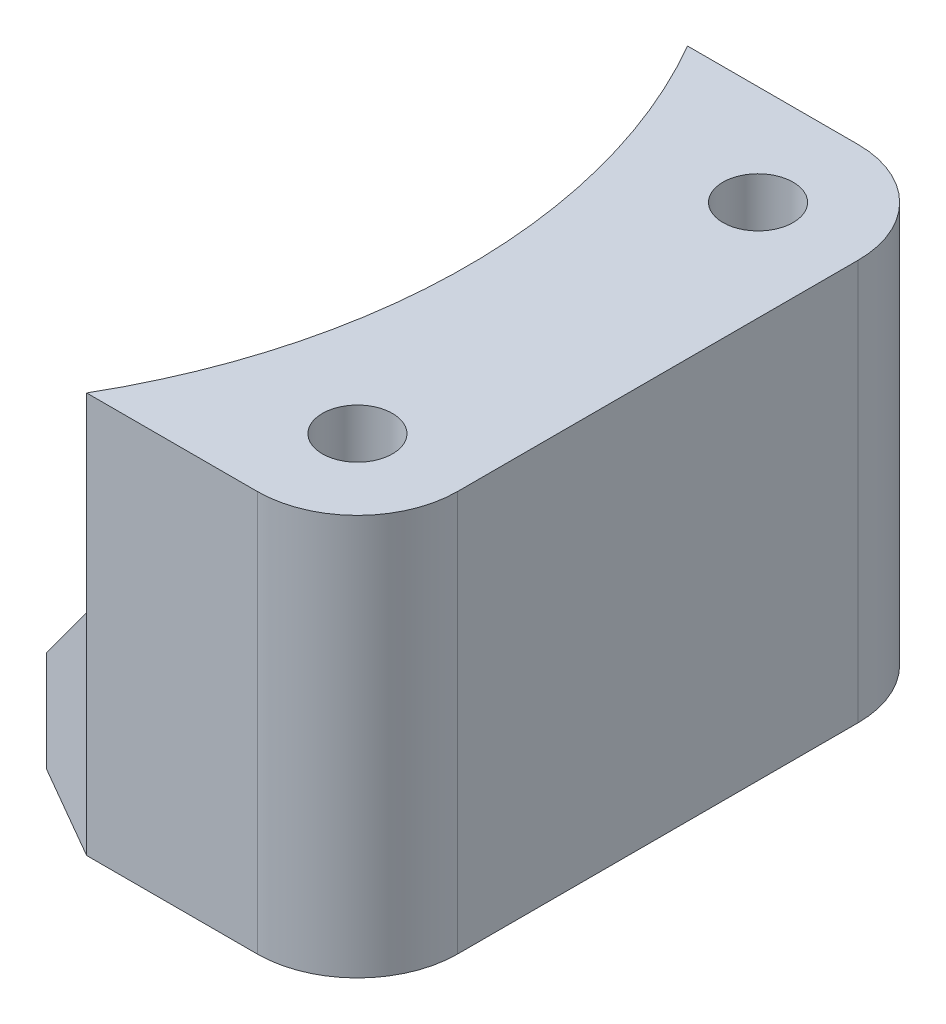
SolidWorks part; units mm, degrees
ref_plane "Front Plane" through (0, 0, 0) normal (0, 0, 1) x (1, 0, 0)
ref_plane "Top Plane" through (0, 0, 0) normal (0, 1, 0) x (1, 0, 0)
ref_plane "Right Plane" through (0, 0, 0) normal (1, 0, 0) x (0, 0, -1)
sketch "Sketch1" plane through (0, 0, 0) normal (0, 0, 1) x (1, 0, 0)
  line L0 (30, 20) -> (30, 10.5)
  line L1 (30, 10.5) -> (24.5, 5)
  line L2 (24.5, 5) -> (24.5, 0)
  line L3 (10.0553, 0) -> (-10.0553, 0) construction
  line L4 (24.5, 0) -> (44.5, 0)
  line L5 (44.5, 0) -> (44.5, 20)
  line L6 (44.5, 20) -> (30, 20)
  line L7 (0, 0) -> (0, 60.3942) construction
  line L8 (0, -11) -> (0, 11) construction
  dimension "D1" = 30
  dimension "D2" = 5
  dimension "D3" = 20
  dimension "D4" = 45
  dimension "D5" = 20
  dimension "D6" = 10.5
revolve "Revolve1" add sketch "Sketch1" angle 60 mid plane about L7
sketch "Sketch2" plane through (0, 0, 0) normal (0, 1, 0) x (1, 0, 0)
  line L0 (-11, 0) -> (11, 0) construction
  line L1 (39.5, -15) -> (11.8624, -15)
  line L2 (39.5, -15) -> (39.5, 15)
  line L3 (39.5, 15) -> (11.8624, 15)
  line L4 (11.8624, -15) -> (11.8624, 15)
  line L5 (0, -11) -> (0, 11) construction
  dimension "D1" = 15
  dimension "D2" = 30
  dimension "D3" = 39.5
extrude "Cut-Extrude2" cut sketch "Sketch2" along normal blind 40 flip side to cut
fillet "Fillet1" radius 5 2 edges at (39.5, 10, -15) (39.5, 10, 15)
sketch "Sketch3" plane through (0, 20, 0) normal (0, 1, 0) x (1, 0, 0)
  line L2 (39.5, 10) -> (39.5, -10) construction
  line L3 (-10.0553, 0) -> (10.0553, 0) construction
  circle A0 centre (34.5, -10) radius 1.75
  circle A1 centre (34.5, 10) radius 1.75
  dimension "D1" = 3.5
  dimension "D2" = 5
  dimension "D3" = 10
  dimension "D4" = 10
extrude "Cut-Extrude3" cut sketch "Sketch3" against normal blind 40
